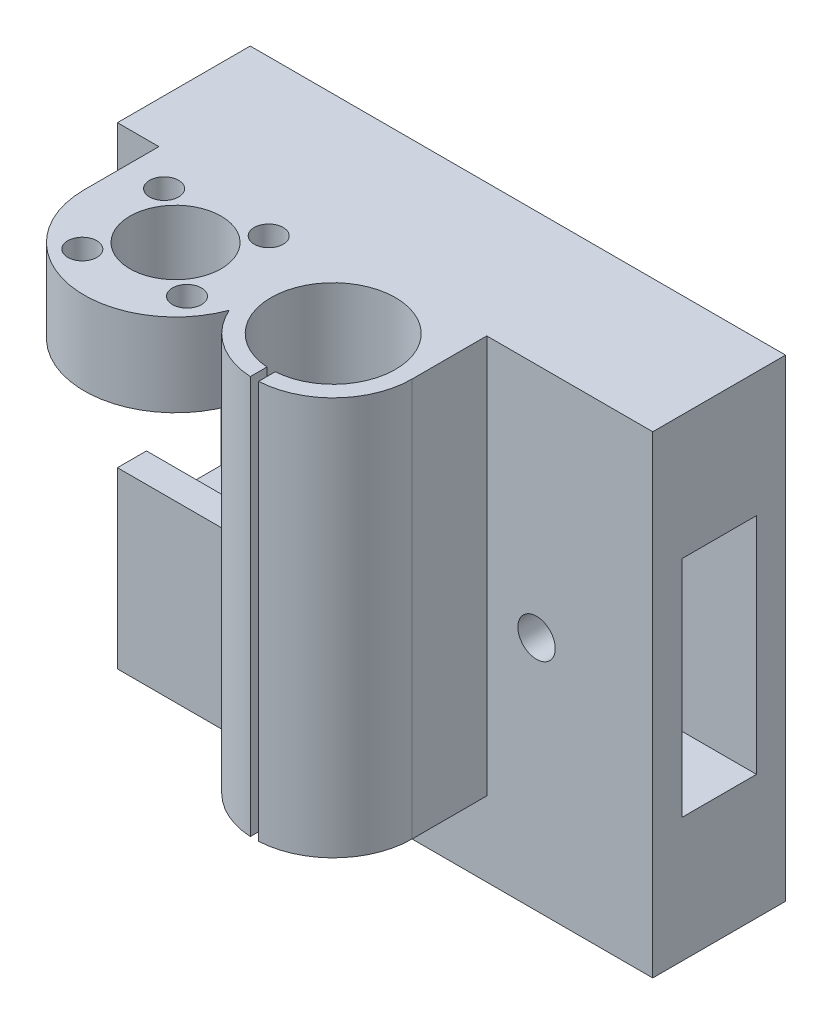
SolidWorks part; units mm, degrees
ref_plane "Front Plane" through (0, 0, 0) normal (0, 0, 1) x (1, 0, 0)
ref_plane "Top Plane" through (0, 0, 0) normal (0, 1, 0) x (1, 0, 0)
ref_plane "Right Plane" through (0, 0, 0) normal (1, 0, 0) x (0, 0, -1)
sketch "Sketch1" plane through (0, 0, 0) normal (0, 1, 0) x (1, 0, 0)
  line L0 (0, 0) -> (64.5, 0)
  line L1 (64.5, 0) -> (64.5, -16)
  line L2 (34.5, -32.4833) -> (34.5, -34.4868)
  line L3 (0, 0) -> (0, -16)
  line L4 (16, -25) -> (35, -25) construction
  line L5 (16, -25) -> (16, 0) construction
  line L6 (16, -25) -> (16, -33) construction
  line L7 (11.0747, -31.3041) -> (20.9253, -18.6959) construction
  line L8 (9.6959, -20.0747) -> (22.3041, -29.9253) construction
  line L9 (35.5, -32.4833) -> (35.5, -34.4868)
  line L10 (35, -25) -> (35, -32.4833) construction
  line L11 (34.5, -32.4833) -> (35.5, -32.4833) construction
  line L12 (34.5, -34.4868) -> (35.5, -34.4868) construction
  line L13 (64.5, -16) -> (44.5, -16)
  line L14 (44.5, -16) -> (44.5, -25)
  line L15 (0, -16) -> (5, -16)
  line L16 (5, -16) -> (5, -25)
  circle A0 centre (16, -25) radius 5.5
  arc A1 (35.5, -32.4833) -> (34.5, -32.4833) centre (35, -25) ccw
  arc A2 (35.5, -34.4868) -> (34.5, -34.4868) centre (35, -25) ccw
  circle A3 centre (16, -25) radius 8 construction
  circle A4 centre (11.0747, -31.3041) radius 1.75
  circle A5 centre (9.6959, -20.0747) radius 1.75
  circle A6 centre (20.9253, -18.6959) radius 1.75
  circle A7 centre (22.3041, -29.9253) radius 1.75
  circle A8 centre (16, -25) radius 11
  dimension "D1" = 19
  dimension "D2" = 15
  dimension "D3" = 11
  dimension "D5" = 2
  dimension "D6" = 16
  dimension "D7" = 38
  dimension "D8" = 3.5
  dimension "D9" = 22
  dimension "D10" = 1
  dimension "D4" = 25
  dimension "D11" = 16
  dimension "D12" = 20
  dimension "D13" = 5
extrude "Boss-Extrude1" add sketch "Sketch1" along normal mid plane 57 contours A8 A2 L0 | A2 A8 A0 A4 A5 A6 A7 | A8 A2 L2 A1 L9 | A2 A8 region at (32.2588, 0, 8.3036) region at (14.1051, 0, 14.4755) region at (41.7013, 0, 31.3574) region at (26.2612, 0, 25)
sketch "Sketch2" plane through (0, 0, 16) normal (0, 0, 1) x (1, 0, 0)
  line L0 (5, 28.5) -> (5, -28.5) construction
  line L1 (5, 18.5) -> (26.3092, 18.5)
  line L2 (5, 18.5) -> (5, -28.5)
  line L3 (5, -28.5) -> (44.5, -28.5)
  line L4 (26.3092, 28.5) -> (26.3092, -28.5) construction
  line L5 (26.3092, 28.5) -> (5, 28.5) construction
  line L6 (26.3092, 18.5) -> (26.3092, -19.5)
  line L7 (26.3092, -19.5) -> (44.5, -19.5)
  line L8 (44.5, 28.5) -> (44.5, -28.5) construction
  line L9 (44.5, -19.5) -> (44.5, -28.5)
  dimension "D1" = 10
  dimension "D2" = 9
extrude "Cut-Extrude1" cut sketch "Sketch2" along normal through all
sketch "Sketch3" plane through (0, 0, 0) normal (-1, 0, 0) x (0, 0, 1)
  line L0 (8, 28.5) -> (8, 13.5) construction
  line L1 (3.5, 13.5) -> (12.5, 13.5)
  line L2 (3.5, 13.5) -> (3.5, -13.5)
  line L3 (3.5, -13.5) -> (12.5, -13.5)
  line L4 (12.5, 13.5) -> (12.5, -13.5)
  line L5 (0, 28.5) -> (16, 28.5) construction
  line L6 (0, 0) -> (3.5, 0) construction
  line L7 (0, 28.5) -> (0, -28.5) construction
  line L8 (0, -28.5) -> (16, -28.5) construction
  dimension "D1" = 3.5
  dimension "D2" = 15
extrude "Cut-Extrude2" cut sketch "Sketch3" against normal through all
sketch "Sketch4" plane through (0, 0, 0) normal (-1, 0, 0) x (0, 0, 1)
  line L0 (16, 28.5) -> (16, -28.5) construction
  line L1 (0, 7.5) -> (16, 7.5)
  line L2 (0, 7.5) -> (0, -7.5)
  line L3 (0, -7.5) -> (16, -7.5)
  line L4 (16, 7.5) -> (16, -7.5)
  point P4 (0, 0)
  point P9 (8, 7.5)
  dimension "D1" = 15
extrude "Cut-Extrude3" cut sketch "Sketch4" against normal up to surface (26.3092 mm away) up to face at (26.3092, -0.5, 22.4183)
hole_wizard "M4 Clearance Hole1" positions "3DSketch1" profile "Sketch5" hole size "M4" standard "ANSI Metric" end condition through all
sketch3d "3DSketch1"
  line L0 (50.5, 0, 16) -> (64.5, 0, 16) construction
  line L6 (64.5, 28.5, 16) -> (64.5, -28.5, 16) construction
  point P0 (50.5, 0, 16)
  dimension "D1" = 14
sketch "Sketch5" plane through (50.5, 0, 16) normal (1, 0, 0) x (0, -1, 0)
  line L0 (0, 0) -> (0, 16)
  line L1 (0, 16) -> (2.25, 16)
  line L2 (2.25, 16) -> (2.25, 0)
  line L5 (2.25, 0) -> (0, 0)
  line L11 (0, -6.35) -> (0, 107.95) construction
  dimension "Thru Hole Dia." = 4.5
  dimension "Thru Hole Depth" = 16
sketch "Sketch6" plane through (0, 0, 0) normal (-1, 0, 0) x (0, 0, 1)
  line L0 (8, -22.5) -> (8, 22.5) construction
  line L1 (8, 22.5) -> (8, 28.5) construction
  line L2 (8, -22.5) -> (8, -28.5) construction
  line L3 (0, -28.5) -> (16, -28.5) construction
  line L4 (0, 28.5) -> (16, 28.5) construction
  circle A0 centre (8, 22.5) radius 4.1
  circle A1 centre (8, -22.5) radius 3.9945
  point P4 (8, -28.5)
  point P9 (8, 28.5)
  dimension "D1" = 45
  dimension "D2" = 8.2
extrude "Cut-Extrude4" cut sketch "Sketch6" against normal blind 30 contours A1 | A0 | A0 region at (0, 22.5, 8) region at (0, -22.5, 8)
